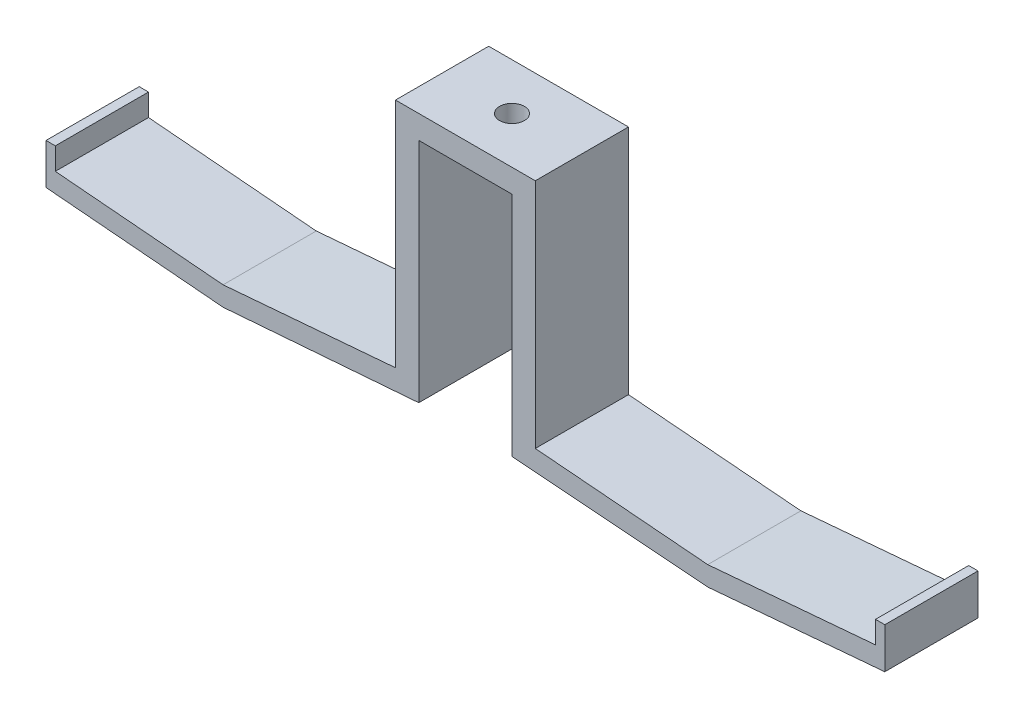
SolidWorks part; units mm, degrees
material "Nylon 6/10"
ref_plane "Front Plane" through (0, 0, 0) normal (0, 0, 1) x (1, 0, 0)
ref_plane "Top Plane" through (0, 0, 0) normal (0, 1, 0) x (1, 0, 0)
ref_plane "Right Plane" through (0, 0, 0) normal (1, 0, 0) x (0, 0, -1)
other "Center of Mass"
sketch "Sketch2" plane through (0, 0, 0) normal (0, 0, 1) x (1, 0, 0)
  line L1 (12.7, 0) -> (12.7, -61.918)
  line L2 (12.7, -61.918) -> (66.04, -66.0514)
  line L3 (66.04, -66.0514) -> (114.3, -61.918)
  line L4 (114.3, -61.918) -> (114.3, -50.8114)
  line L5 (111.76, -50.8114) -> (111.76, -56.838)
  line L6 (111.76, -56.838) -> (66.04, -60.7538)
  line L19 (114.3, -50.8114) -> (111.76, -50.8114)
  line L20 (0, 125.2351) -> (0, -75.9356) construction
  line L21 (12.7, 0) -> (-12.7, 0)
  line L22 (0, 0) -> (0, 6.35)
  line L23 (19.05, 6.35) -> (-19.05, 6.35)
  line L24 (19.05, 6.35) -> (19.05, 0)
  line L25 (19.05, 0) -> (19.05, -56.838)
  line L26 (19.05, -56.838) -> (66.04, -60.7538)
  line L27 (-19.05, 0) -> (-19.05, -56.838)
  line L28 (-19.05, 6.35) -> (-19.05, 0)
  line L29 (-12.7, 0) -> (-12.7, -61.918)
  line L30 (-12.7, -61.918) -> (-66.04, -66.0514)
  line L31 (-66.04, -66.0514) -> (-114.3, -61.918)
  line L32 (-114.3, -61.918) -> (-114.3, -50.8114)
  line L33 (-114.3, -50.8114) -> (-111.76, -50.8114)
  line L34 (-111.76, -50.8114) -> (-111.76, -56.838)
  line L35 (-111.76, -56.838) -> (-66.04, -60.7538)
  line L36 (-19.05, -56.838) -> (-66.04, -60.7538)
  dimension "D1" = 19.05
  dimension "D2" = 12.7
  dimension "D3" = 56.838
  dimension "D4" = 3.9158
  dimension "D5" = 61.918
  dimension "D6" = 2.54
  dimension "D7" = 45.72
  dimension "D8" = 46.99
  dimension "D9" = 15.24
  dimension "D10" = 6.35
extrude "Boss-Extrude1" add sketch "Sketch2" along normal blind 25.4 contours L26 L25 L24 L23 L22 L21 L1 L2 L3 L4 L19 L5 L6 | L27 L36 L35 L34 L33 L32 L31 L30 L29 L21 L22 L23 L28 region at (6.35, 1.353, 0) region at (-6.35, 1.353, 0)
hole_wizard "1/4 Clearance Hole1" positions "Sketch3" profile "Sketch4" hole size "1/4" standard "ANSI Inch"
sketch "Sketch3" plane through (0, 6.35, 0) normal (0, 1, 0) x (1, 0, 0)
  line L0 (-19.05, -25.4) -> (-19.05, 0) construction
  line L2 (19.05, 0) -> (-19.05, 0) construction
  point P0 (0, -12.7)
  dimension "D1" = 19.05
  dimension "D2" = 12.7
sketch "Sketch4" plane through (0, 6.35, 12.7) normal (1, 0, 0) x (0, 0, 1)
  line L0 (0, 0) -> (0, 52.8298)
  line L1 (0, 52.8298) -> (3.3782, 50.8)
  line L2 (3.3782, 50.8) -> (3.3782, 0)
  line L5 (3.3782, 0) -> (0, 0)
  line L10 (0, 52.8298) -> (-3.3782, 50.8) construction
  line L11 (0, -6.35) -> (0, 107.95) construction
  dimension "Hole Dia." = 6.7564
  dimension "Hole Depth" = 50.8
  dimension "Drill Angle" = 118
